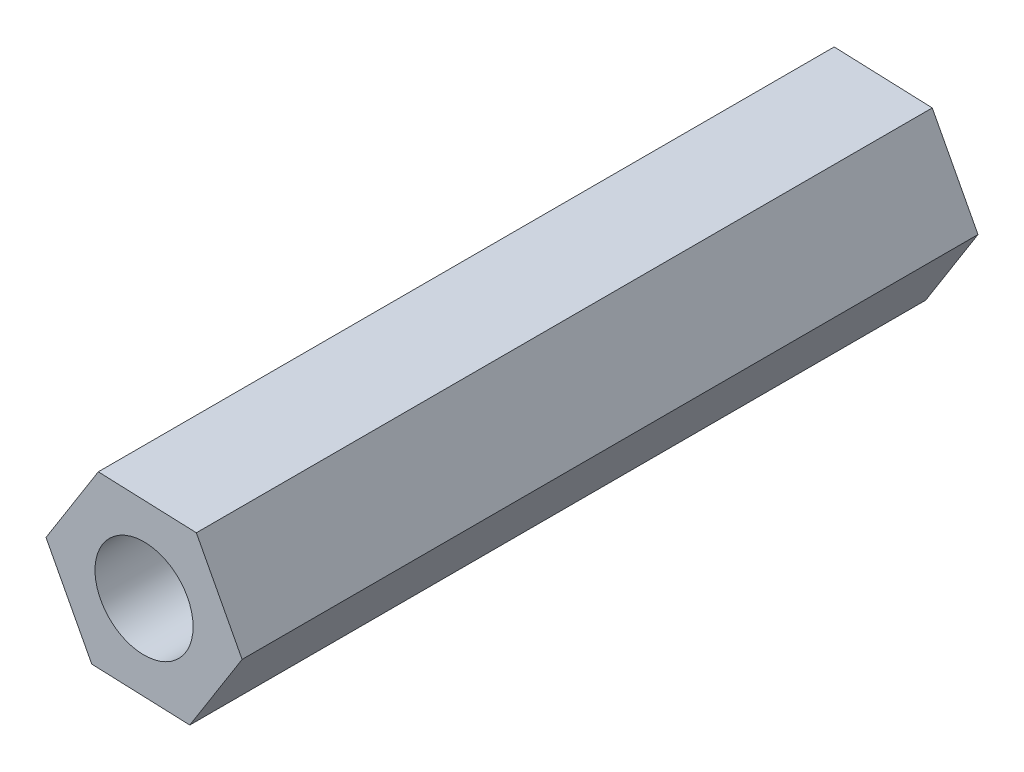
SolidWorks part; units mm, degrees
material "6061 Alloy"
ref_plane "前视基准面" through (0, 0, 0) normal (0, 0, 1) x (1, 0, 0)
ref_plane "上视基准面" through (0, 0, 0) normal (0, 1, 0) x (1, 0, 0)
ref_plane "右视基准面" through (0, 0, 0) normal (1, 0, 0) x (0, 0, -1)
sketch "Sketch1" plane through (0, 0, 0) normal (0, 0, 1) x (1, 0, 0)
  line L1 (5.0734, -119.5568) -> (1.0763, -119.4024)
  line L2 (1.0763, -119.4024) -> (-1.0559, -122.7867)
  line L3 (-1.0559, -122.7867) -> (0.8089, -126.3254)
  line L4 (0.8089, -126.3254) -> (4.8059, -126.4799)
  line L5 (4.8059, -126.4799) -> (6.9381, -123.0955)
  line L6 (6.9381, -123.0955) -> (5.0734, -119.5568)
  circle A0 centre (2.9411, -122.9411) radius 3.4641 construction
  circle A1 centre (2.9411, -122.9411) radius 2
  dimension "D2" = 4
  dimension "D1" = 4
extrude "Boss-Extrude1" add sketch "Sketch1" along normal blind 30
